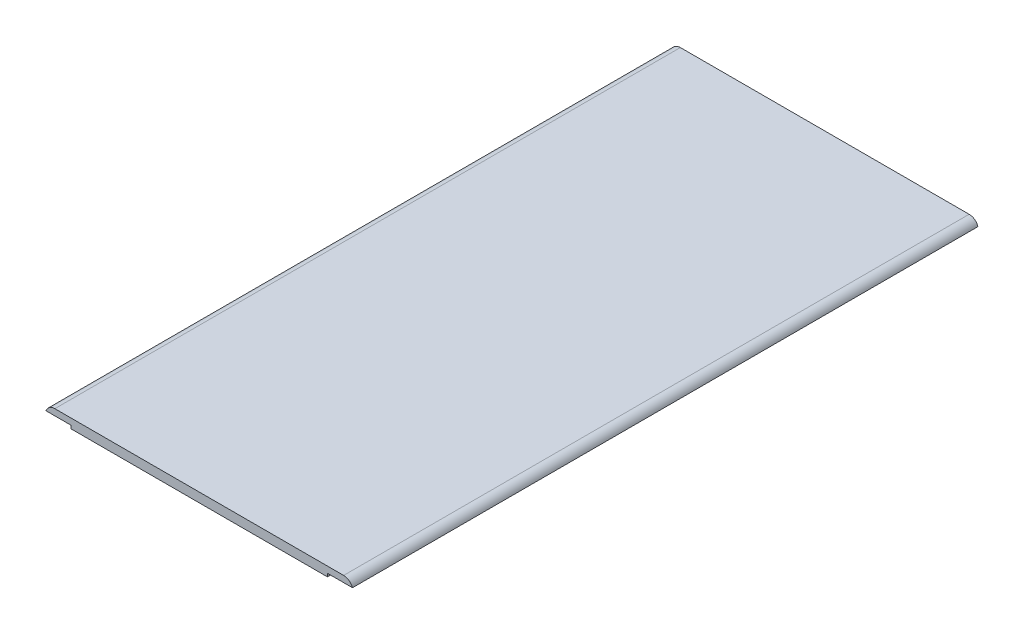
SolidWorks part; units mm, degrees
ref_plane "Ebene vorne" through (0, 0, 0) normal (0, 0, 1) x (1, 0, 0)
ref_plane "Ebene oben" through (0, 0, 0) normal (0, 1, 0) x (1, 0, 0)
ref_plane "Ebene rechts" through (0, 0, 0) normal (1, 0, 0) x (0, 0, -1)
sketch "Skizze2" plane through (0, 0, 0) normal (0, 1, 0) x (1, 0, 0)
  line L0 (-49, 0) -> (49, 0) construction
  line L1 (-49, 100) -> (49, 100)
  line L2 (-49, 100) -> (-49, -100)
  line L3 (-49, -100) -> (49, -100)
  line L4 (49, 100) -> (49, -100)
  dimension "D1" = 98
  dimension "D2" = 200
extrude "Aufsatz-Linear austragen2" add sketch "Skizze2" along normal mid plane 3
sketch "Skizze4" plane through (0, -1.5, 0) normal (0, -1, 0) x (1, 0, 0)
  line L0 (49, -100) -> (-49, -100) construction
  line L1 (-49, 100) -> (-41, 100)
  line L2 (-49, 100) -> (-49, -100)
  line L3 (-49, -100) -> (-41, -100)
  line L4 (-41, 100) -> (-41, -100)
  line L6 (49, 100) -> (41, 100)
  line L7 (49, 100) -> (49, -100)
  line L8 (49, -100) -> (41, -100)
  line L9 (41, 100) -> (41, -100)
  dimension "D1" = 8
extrude "Schnitt-Linear austragen1" cut sketch "Skizze4" against normal blind 1
fillet "Verrundung1" radius 3 2 edges at (-49, 1.5, 0) (49, 1.5, 0)
sketch "Skizze5" plane through (0, -1.5, 0) normal (0, -1, 0) x (1, 0, 0)
  line L0 (-12.5, -80.75) -> (12.5, -80.75) construction
  line L1 (0, -80.75) -> (0, 0) construction
  line L13 (-12.5, -65.75) -> (12.5, -65.75)
  line L14 (-12.5, -65.75) -> (-12.5, -95.75)
  line L15 (-12.5, -95.75) -> (12.5, -95.75)
  line L16 (12.5, -65.75) -> (12.5, -95.75)
  dimension "D1" = 80.75
  dimension "D2" = 30
  dimension "D3" = 25
extrude "Schnitt-Linear austragen2" cut sketch "Skizze5" against normal blind 2.5
fillet "Verrundung2" radius 5 4 edges at (12.5, -0.25, -65.75) (12.5, -0.25, -95.75) (-12.5, -0.25, -95.75) (-12.5, -0.25, -65.75)
